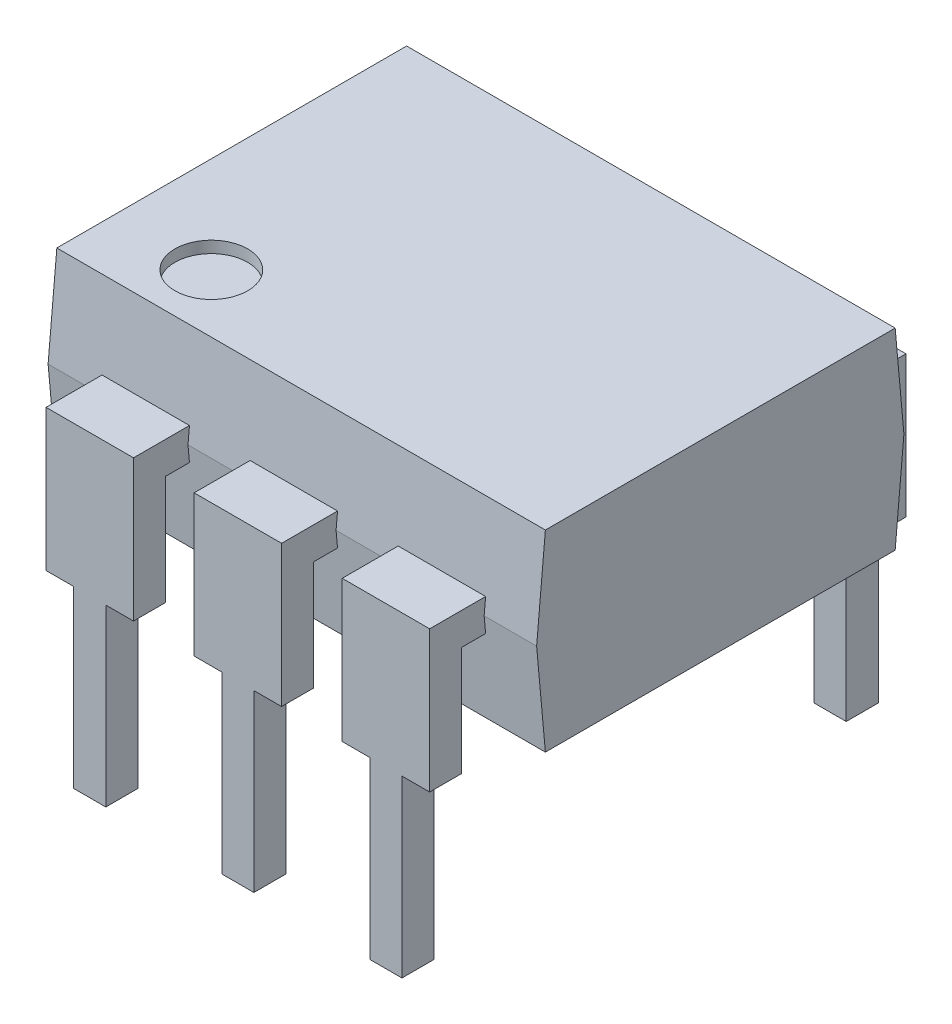
SolidWorks part; units mm, degrees
ref_plane "Front Plane" through (0, 0, 0) normal (0, 0, 1) x (1, 0, 0)
ref_plane "Top Plane" through (0, 0, 0) normal (0, 1, 0) x (1, 0, 0)
ref_plane "Right Plane" through (0, 0, 0) normal (1, 0, 0) x (0, 0, -1)
sketch "Sketch2" plane through (0, 0, 0) normal (1, 0, 0) x (0, 0, -1)
  line L0 (0, 0) -> (0, 3.3)
  line L1 (0, 3.3) -> (-3, 3.3)
  line L2 (-3, 3.3) -> (-3.15, 1.65)
  line L3 (-3.15, 1.65) -> (-3, 0)
  line L4 (-3, 0) -> (0, 0)
  line L5 (-3.15, 1.65) -> (0, 1.65) construction
  line L6 (-3, 3.3) -> (-3, 0) construction
  dimension "D1" = 3.3
  dimension "D2" = 3.15
  dimension "D3" = 3
extrude "Boss-Extrude1" add sketch "Sketch2" along normal blind 8.38
sketch "Sketch3" plane through (0, 0, 0) normal (0, 1, 0) x (1, 0, 0)
  line L0 (1.375, -3.535) -> (1.925, -4.085) construction
  line L1 (1.375, -4.085) -> (1.925, -4.085)
  line L2 (1.375, -4.085) -> (1.375, -3.535)
  line L3 (1.375, -3.535) -> (1.925, -3.535)
  line L4 (1.925, -4.085) -> (1.925, -3.535)
  line L5 (1.925, -3.535) -> (1.375, -4.085) construction
  point P4 (1.65, -3.81)
  dimension "D1" = 0.55
  dimension "D2" = 3.81
  dimension "D3" = 1.65
ref_plane "Plane1" through (0, 1.65, 0) normal (0, 1, 0) x (1, 0, 0)
sketch "Sketch5" plane through (0, 1.65, 0) normal (0, 1, 0) x (1, 0, 0)
  line L1 (0.9, -4.085) -> (2.4, -4.085)
  line L2 (0.9, -4.085) -> (0.9, -3)
  line L3 (0.9, -3) -> (2.4, -3)
  line L4 (2.4, -4.085) -> (2.4, -3)
  line L5 (8.38, -3) -> (0, -3) construction
  line L6 (1.375, -4.085) -> (1.925, -4.085) construction
  line L7 (0.9, -3.535) -> (2.4, -3.535)
  line L8 (1.375, -3.535) -> (1.925, -3.535) construction
  line L9 (0.9, -3.535) -> (9.144, -3.535) construction
  point P12 (1.65, -4.085)
  point P15 (1.65, -4.085)
  dimension "D1" = 1.5
extrude "Boss-Extrude2" add sketch "Sketch5" along normal mid plane 0.55 separate body contours L7 L2 L1 L4 | L2 L7 L4 L3 region at (1.65, 1.65, 3.81) region at (1.65, 1.65, 3.2675)
extrude "Boss-Extrude4" add sketch "Sketch5<3>" against normal blind 2.15 contours L7 L2 L1 L4 region at (1.65, 1.65, 3.81)
sketch "Sketch5<3>" plane through (0, 1.65, 0) normal (0, 1, 0) x (1, 0, 0) same geometry as "Sketch5"
extrude "Boss-Extrude5" add sketch "Sketch3" against normal blind 3.5
pattern_linear "LPattern1" count 3 spacing 2.54 along (1, 0, 0) of "Boss-Extrude2", "Boss-Extrude5", "Boss-Extrude4"
mirror "Mirror2" about plane through (0, 0, 0) normal (0, 0, 1) of "Boss-Extrude1"
mirror "Mirror3" about plane through (0, 0, 0) normal (0, 0, 1) of "LPattern1", "Boss-Extrude5", "Boss-Extrude4", "Boss-Extrude2"
sketch "Sketch6" plane through (0, 3.3, 0) normal (0, 1, 0) x (1, 0, 0)
  line L0 (1.65, -2) -> (1.65, -3.81) construction
  circle A0 centre (1.65, -2) radius 0.6237
  dimension "D1" = 2
extrude "Cut-Extrude1" cut sketch "Sketch6" against normal blind 0.2
ref_axis "Axis1" through (1.65, 0, 3.81) along (0, -1, 0)
